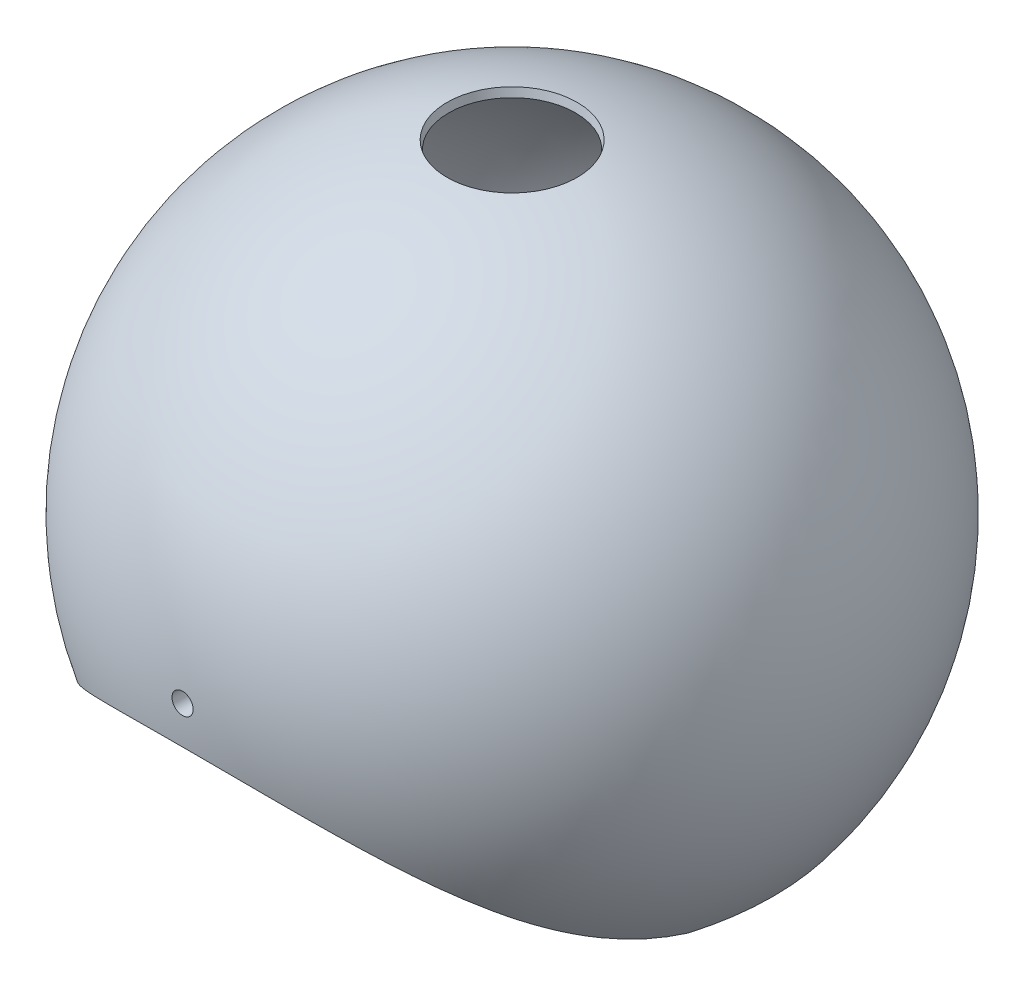
SolidWorks part; units mm, degrees
ref_plane "Front Plane" through (0, 0, 0) normal (0, 0, 1) x (1, 0, 0)
ref_plane "Top Plane" through (0, 0, 0) normal (0, 1, 0) x (1, 0, 0)
ref_plane "Right Plane" through (0, 0, 0) normal (1, 0, 0) x (0, 0, -1)
sketch "Sketch1" plane through (0, 0, 0) normal (0, 0, 1) x (1, 0, 0)
  line L0 (0, 0) -> (0, 78) construction
  line L1 (-61.7509, -47.6532) -> (-59.2045, -47.6532)
  line L3 (-15.3947, 76.4657) -> (-15, 74.505)
  arc A0 (-15.3947, 76.4657) -> (-61.7509, -47.6532) centre (0, 0) ccw
  arc A1 (-15, 74.505) -> (-59.2045, -47.6532) centre (0, 0) ccw
  dimension "D1" = 78
  dimension "D2" = 2
  dimension "D3" = 15
revolve "Revolve1" add sketch "Sketch1" angle 360 about L0
ref_plane "Plane1" through (0, 0, 77) normal (0, 0, 1) x (1, 0, 0)
sketch "Sketch2" plane through (0, 0, 77) normal (0, 0, 1) x (1, 0, 0)
  circle A0 centre (0, 0) radius 5
  dimension "D1" = 10
extrude "Boss-Extrude1" add sketch "Sketch2" against normal blind 10 contours A0
ref_plane "Plane3" through (0, 0, -77) normal (0, 0, 1) x (1, 0, 0)
sketch "Sketch11" plane through (0, 0, -77) normal (0, 0, 1) x (1, 0, 0)
  circle A0 centre (0, 0) radius 5
  dimension "D1" = 10
ref_axis "Axis1" through (0, 76.4657, 0) along (0, -1, 0)
sketch "Sketch5" plane through (0, 0, 67) normal (0, 0, -1) x (-1, 0, 0)
  circle A0 centre (0, 0) radius 2.45
  dimension "D1" = 4.9
extrude "Cut-Extrude2" cut sketch "Sketch5" against normal blind 3
ref_plane "Plane4" through (0, 0, 72) normal (0, 0, -1) x (-1, 0, 0)
sketch "Sketch6" plane through (0, 0, 72) normal (0, 0, -1) x (-1, 0, 0)
  circle A0 centre (0, 0) radius 2.5
  dimension "D1" = 5
sketch "Sketch7" plane through (0, 0, 70) normal (0, 0, -1) x (-1, 0, 0)
  circle A0 centre (0, 0) radius 1
  dimension "D1" = 2
extrude "Cut-Extrude3" cut sketch "Sketch6" against normal blind 13
extrude "Cut-Extrude4" cut sketch "Sketch7" against normal blind 13
sketch "Sketch8" plane through (0, 0, 77) normal (0, 0, 1) x (1, 0, 0)
  line L0 (59.2045, -47.6532) -> (-59.2045, -47.6532)
  line L1 (-61.7509, -47.6532) -> (61.7509, -47.6532) construction
  line L2 (-59.2045, -47.6532) -> (59.2045, -47.6532) construction
  arc A0 (59.2045, -47.6532) -> (-59.2045, -47.6532) centre (0, -74.4828) ccw
  point P3 (0, 11.2595)
  point P4 (0, 0)
  point P5 (0, -26.2313)
  point P6 (0, 0)
  point P7 (55.5479, -43.9639)
  point P9 (-48.9249, -98.6573)
  point P15 (53.219, -47.6532)
  point P19 (0, 0)
  point P21 (0, 0)
  dimension "D1" = 65
extrude "Cut-Extrude5" cut sketch "Sketch8" against normal through all and the other way through all contours A0 L0
sketch "Sketch9" plane through (0, 0, 0) normal (1, 0, 0) x (0, 0, -1)
  line L0 (-24.7996, 42.3678) -> (-18.5037, 44.6594)
  line L1 (-18.5037, 44.6594) -> (-18.5037, 74.505)
  line L3 (-18.5037, 74.505) -> (-27.091, 71.3795)
  line L4 (-27.091, 71.3795) -> (-35.4897, 67.6905)
  line L5 (-35.4897, 67.6905) -> (-39.9781, 64.8692)
  line L6 (-39.9781, 64.8692) -> (-24.7996, 42.3678)
  point P6 (0, 0)
  point P7 (0, 0)
  point P9 (0, 0)
  point P11 (0, 0)
  point P12 (0, 0)
extrude "Boss-Extrude2" add sketch "Sketch9" along normal blind 8 and the other way blind 10 contours L6 L0 L1 L3 L4 L5
sketch "Sketch10" plane through (0, 45.3822, 16.5178) normal (0, -0.9397, -0.342) x (1, 0, 0)
  circle A0 centre (-4.0021, 5.5134) radius 1.4
  circle A1 centre (2.3979, 5.5134) radius 1.4
  dimension "D1" = 2.8
  dimension "D2" = 2.8
extrude "Cut-Extrude6" cut sketch "Sketch10" against normal blind 8
extrude "Boss-Extrude3" add sketch "Sketch11" along normal blind 6
sketch "Sketch12" plane through (0, 0, -71) normal (0, 0, 1) x (1, 0, 0)
  circle A0 centre (0, 0) radius 3
  circle A1 centre (0, 0) radius 5
  dimension "D1" = 10
  dimension "D2" = 6
extrude "Cut-Extrude8" cut sketch "Sketch12" against normal blind 1
sketch "Sketch13" plane through (0, 0, -71) normal (0, 0, 1) x (1, 0, 0)
  circle A0 centre (0, 0) radius 1.9
  dimension "D1" = 3.8
extrude "Cut-Extrude9" cut sketch "Sketch13" against normal blind 5
